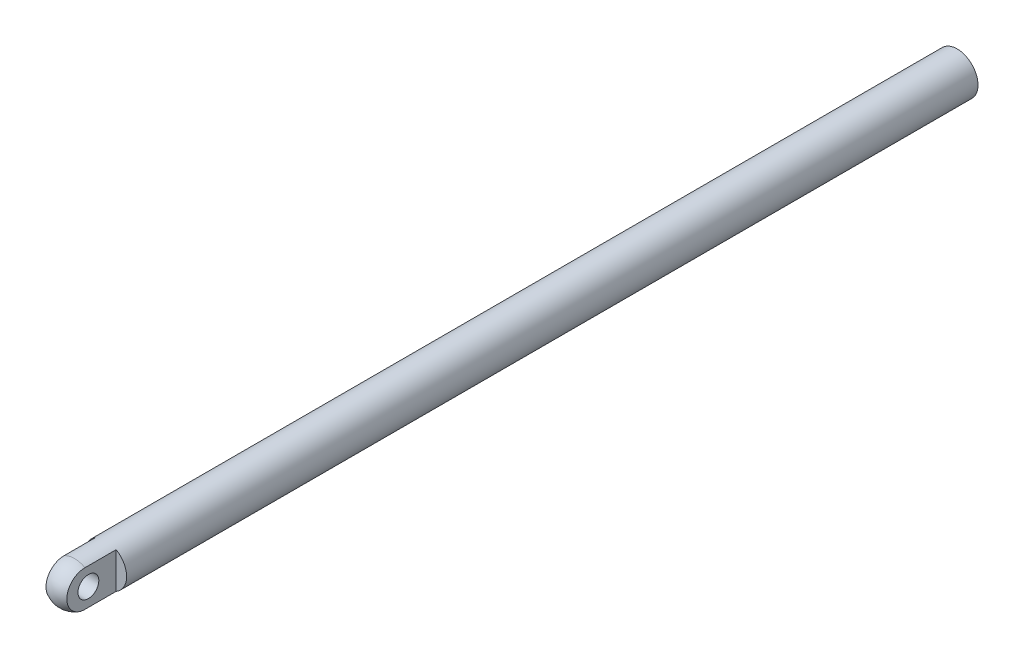
SolidWorks part; units mm, degrees
ref_plane "前视基准面" through (0, 0, 0) normal (0, 0, 1) x (1, 0, 0)
ref_plane "上视基准面" through (0, 0, 0) normal (0, 1, 0) x (1, 0, 0)
ref_plane "右视基准面" through (0, 0, 0) normal (1, 0, 0) x (0, 0, -1)
sketch "草图1" plane through (0, 0, 0) normal (0, 0, 1) x (1, 0, 0)
  circle A0 centre (0, 0) radius 60
extrude "凸台-拉伸1" add sketch "草图1" along normal blind 2600
sketch "草图2" plane through (0, 0, 2600) normal (0, 0, 1) x (1, 0, 0)
  line L1 (-30, 60) -> (-30, -60)
  line L2 (30, 60) -> (30, -60)
  line L3 (30, 60) -> (93.7325, 30.2245)
  line L4 (93.7325, 30.2245) -> (81.9854, -33.1612)
  line L5 (81.9854, -33.1612) -> (32.06, -60)
  line L6 (32.06, -60) -> (30, -60)
  line L7 (-30, -60) -> (-70.483, -43.44)
  line L8 (-70.483, -43.44) -> (-92.9983, 12.8485)
  line L9 (-92.9983, 12.8485) -> (-30, 60)
extrude "切除-拉伸2" cut sketch "草图2" against normal blind 150
sketch "草图3" plane through (30, 0, 0) normal (1, 0, 0) x (0, 0, -1)
  line L0 (-2450, 51.9615) -> (-2450, -51.9615) construction
  circle A0 centre (-2530, 0) radius 30
  dimension "D1" = 80
extrude "切除-拉伸3" cut sketch "草图3" against normal blind 150
fillet "圆角2" radius 60 1 edges at (0, 60, 2600)
scale "缩放比例1" scale about origin uniform scaling yes scale factor 0.345
